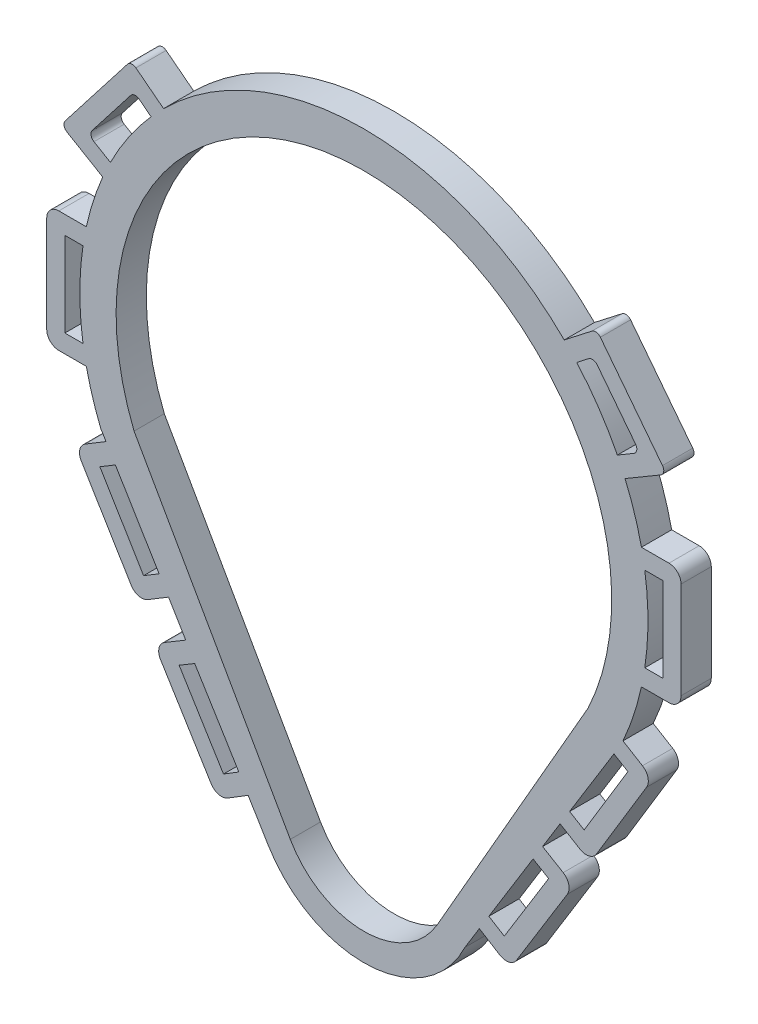
SolidWorks part; units mm, degrees
ref_plane "Front Plane" through (0, 0, 0) normal (0, 0, 1) x (1, 0, 0)
ref_plane "Top Plane" through (0, 0, 0) normal (0, 1, 0) x (1, 0, 0)
ref_plane "Right Plane" through (0, 0, 0) normal (1, 0, 0) x (0, 0, -1)
sketch "Sketch1" plane through (0, 0, 0) normal (0, 0, 1) x (1, 0, 0)
  line L0 (0, 41) -> (0, -67) construction
  line L5 (0, 0) -> (0, -54) construction
  line L6 (37.1057, -17.4403) -> (11.3127, -72.3172) construction
  line L7 (42.5358, -19.9925) -> (16.7428, -74.8694) construction
  line L8 (-38.0251, -15.3328) -> (-11.3182, -72.3056) construction
  line L9 (-43.5255, -17.735) -> (-16.7509, -74.8522) construction
  line L10 (-38.0251, -15.3328) -> (-12.1778, -60.9066)
  line L11 (-43.5255, -17.735) -> (-15.8341, -63.5669)
  line L12 (37.1057, -17.4403) -> (12.1446, -60.9649)
  line L13 (42.5358, -19.9925) -> (16.7077, -61.9433)
  arc A0 (37.1057, -17.4403) -> (-38.0251, -15.3328) centre (0, 0) ccw
  arc A2 (42.5358, -19.9925) -> (-43.5255, -17.735) centre (0, 0) ccw
  arc A4 (-12.1778, -60.9066) -> (12.1446, -60.9649) centre (0, -54) ccw
  arc A5 (-16.7509, -74.8522) -> (16.7428, -74.8694) centre (0, -67) ccw construction
  arc A6 (-11.3182, -72.3056) -> (11.3127, -72.3172) centre (0, -67) ccw construction
  arc A7 (-15.8341, -63.5669) -> (16.7077, -61.9433) centre (0, -54) ccw
  dimension "D1" = 6
  dimension "D2" = 41
  dimension "D3" = 14
  dimension "D6" = 18.4999
  dimension "D4" = 67
  dimension "D5" = 54
extrude "Boss-Extrude1" add sketch "Sketch1" along normal blind 5
sketch "Sketch3" plane through (0, 0, 5) normal (0, 0, 1) x (1, 0, 0)
  line L0 (-35.214, 31.1284) -> (-37.1889, 32.6612)
  line L1 (-41.9377, 21.2186) -> (-44.6629, 22.8236)
  line L2 (-38.592, 32.4844) -> (-44.9454, 24.2984)
  line L3 (-35.214, 31.1284) -> (-41.9377, 21.2186)
  line L4 (-31.1514, 31.7728) -> (-37.7195, 36.8706)
  line L5 (-39.1226, 36.6937) -> (-49.4061, 23.444)
  line L6 (-41.0353, 17.2054) -> (-49.1237, 21.9692)
  line L7 (-31.1514, 31.7728) -> (-41.0353, 17.2054)
  line L8 (0, 0) -> (0, 76.5871) construction
  line L17 (-35.214, 31.1284) -> (-37.9789, 33.2743) construction
  line L18 (-37.9789, 33.2743) -> (-45.6424, 23.4005) construction
  line L19 (-31.1514, 31.7728) -> (-38.5094, 37.4837) construction
  line L20 (-38.5094, 37.4837) -> (-50.1031, 22.5461) construction
  line L21 (-41.0353, 17.2054) -> (-50.1031, 22.5461) construction
  line L22 (-41.9377, 21.2186) -> (-45.6424, 23.4005) construction
  line L23 (31.1514, 31.7728) -> (41.0353, 17.2054)
  line L24 (41.0353, 17.2054) -> (49.1237, 21.9692)
  line L25 (39.1226, 36.6937) -> (49.4061, 23.444)
  line L26 (31.1514, 31.7728) -> (37.7195, 36.8706)
  line L27 (35.214, 31.1284) -> (41.9377, 21.2186)
  line L28 (38.592, 32.4844) -> (44.9454, 24.2984)
  line L29 (41.9377, 21.2186) -> (44.6629, 22.8236)
  line L30 (35.214, 31.1284) -> (37.1889, 32.6612)
  circle A0 centre (38.8928, 26.3885) radius 6 construction
  circle A1 centre (-38.8928, 26.3885) radius 6 construction
  arc A2 (42.5358, -19.9925) -> (-43.5255, -17.735) centre (0, 0) ccw construction
  arc A3 (44.6629, 22.8236) -> (44.9454, 24.2984) centre (44.1554, 23.6853) ccw
  arc A4 (-37.1889, 32.6612) -> (-38.592, 32.4844) centre (-37.8021, 31.8712) ccw
  arc A5 (-37.7195, 36.8706) -> (-39.1226, 36.6937) centre (-38.3326, 36.0806) ccw
  arc A6 (-49.1237, 21.9692) -> (-49.4061, 23.444) centre (-48.6162, 22.8309) cw
  arc A7 (-44.6629, 22.8236) -> (-44.9454, 24.2984) centre (-44.1554, 23.6853) cw
  arc A12 (49.1237, 21.9692) -> (49.4061, 23.444) centre (48.6162, 22.8309) ccw
  arc A13 (37.7195, 36.8706) -> (39.1226, 36.6937) centre (38.3326, 36.0806) cw
  arc A14 (37.1889, 32.6612) -> (38.592, 32.4844) centre (37.8021, 31.8712) cw
  point P29 (-39.9539, 34.8072)
  point P33 (-38.5094, 37.4837)
  point P48 (38.5094, 37.4837)
  point P49 (39.9539, 34.8072)
  dimension "D1" = 3
  dimension "D2" = 12
  dimension "D3" = 2.5
extrude "1" add sketch "Sketch3" against normal blind 5
sketch "Sketch4" plane through (0, 0, 5) normal (0, 0, 1) x (1, 0, 0)
  line L2 (0, 0) -> (0, 26.9586) construction
  line L5 (-46.4758, 7) -> (-46.4758, -7)
  line L6 (-46.4758, 7) -> (-49.4758, 7)
  line L7 (-49.4758, 7) -> (-49.4758, -7)
  line L8 (-49.4758, -7) -> (-46.4758, -7)
  line L9 (-43.4758, 10) -> (-50.4758, 10)
  line L10 (-52.4758, 8) -> (-52.4758, -8)
  line L11 (-50.4758, -10) -> (-43.4758, -10)
  line L12 (-43.4758, 10) -> (-43.4758, -10)
  line L13 (43.4758, 10) -> (43.4758, -10)
  line L14 (50.4758, -10) -> (43.4758, -10)
  line L15 (52.4758, 8) -> (52.4758, -8)
  line L16 (43.4758, 10) -> (50.4758, 10)
  line L17 (49.4758, -7) -> (46.4758, -7)
  line L18 (49.4758, 7) -> (49.4758, -7)
  line L19 (46.4758, 7) -> (49.4758, 7)
  line L20 (46.4758, 7) -> (46.4758, -7)
  line L21 (-52.4758, -10) -> (-43.4758, -10) construction
  line L22 (-52.4758, 10) -> (-52.4758, -10) construction
  line L23 (-43.4758, 10) -> (-52.4758, 10) construction
  arc A0 (50.4758, -10) -> (52.4758, -8) centre (50.4758, -8) ccw
  arc A5 (-43.2114, 18.4871) -> (-43.5255, -17.735) centre (0, 0) ccw construction
  arc A6 (52.4758, 8) -> (50.4758, 10) centre (50.4758, 8) ccw
  arc A7 (-50.4758, -10) -> (-52.4758, -8) centre (-50.4758, -8) cw
  arc A8 (-52.4758, 8) -> (-50.4758, 10) centre (-50.4758, 8) cw
  point P24 (52.4758, -10)
  point P27 (52.4758, 10)
  point P31 (-52.4758, -10)
  dimension "D1" = 2
  dimension "D2" = 14
  dimension "D3" = 3
  dimension "D4" = 3
extrude "2" add sketch "Sketch4" against normal blind 5
sketch "Sketch5" plane through (0, 0, 5) normal (0, 0, 1) x (1, 0, 0)
  line L0 (-41.1186, -21.7187) -> (-43.6863, -23.2701)
  line L1 (-43.5255, -17.735) -> (-15.8341, -63.5669) construction
  line L2 (-43.6863, -23.2701) -> (-36.4464, -35.2528)
  line L3 (-36.4464, -35.2528) -> (-33.8787, -33.7014)
  line L4 (-41.1186, -21.7187) -> (-33.8787, -33.7014)
  line L5 (-40.1022, -17.5996) -> (-46.0936, -21.2196)
  line L6 (-46.7711, -23.9656) -> (-38.497, -37.6601)
  line L7 (-35.7509, -38.3377) -> (-29.7596, -34.7177)
  line L8 (-40.1022, -17.5996) -> (-29.7596, -34.7177)
  line L9 (0, 0) -> (0, -46.5074) construction
  line L10 (40.1022, -17.5996) -> (29.7596, -34.7177)
  line L11 (35.7509, -38.3377) -> (29.7596, -34.7177)
  line L12 (46.7711, -23.9656) -> (38.497, -37.6601)
  line L13 (40.1022, -17.5996) -> (46.0936, -21.2196)
  line L14 (41.1186, -21.7187) -> (33.8787, -33.7014)
  line L15 (36.4464, -35.2528) -> (33.8787, -33.7014)
  line L16 (43.6863, -23.2701) -> (36.4464, -35.2528)
  line L17 (41.1186, -21.7187) -> (43.6863, -23.2701)
  line L18 (-37.4627, -39.3719) -> (-29.7596, -34.7177) construction
  line L19 (-47.8054, -22.2538) -> (-37.4627, -39.3719) construction
  line L20 (-40.1022, -17.5996) -> (-47.8054, -22.2538) construction
  arc A0 (-35.7509, -38.3377) -> (-38.497, -37.6601) centre (-36.7852, -36.6259) cw
  arc A1 (-46.7711, -23.9656) -> (-46.0936, -21.2196) centre (-45.0593, -22.9314) cw
  arc A2 (35.7509, -38.3377) -> (38.497, -37.6601) centre (36.7852, -36.6259) ccw
  arc A3 (46.0936, -21.2196) -> (46.7711, -23.9656) centre (45.0593, -22.9314) cw
  point P24 (-37.4627, -39.3719)
  point P30 (37.4627, -39.3719)
  dimension "D4" = 2
  dimension "D1" = 3
  dimension "D2" = 14
  dimension "D3" = 3
extrude "3" add sketch "Sketch5" against normal blind 5
sketch "Sketch2" plane through (0, 0, 5) normal (0, 0, 1) x (1, 0, 0)
  line L1 (34.7204, -44.1302) -> (26.9879, -39.5238) construction
  line L4 (0, 49.5385) -> (0, -93.5909) construction
  line L18 (27.9925, -43.6143) -> (20.6756, -55.4986)
  line L19 (16.7077, -61.9433) -> (32.4639, -36.3517) construction
  line L20 (20.6756, -55.4986) -> (23.2302, -57.0715)
  line L21 (23.2302, -57.0715) -> (30.5698, -45.1496)
  line L22 (30.5698, -45.1496) -> (27.9925, -43.6143)
  line L23 (25.2606, -59.4958) -> (33.6565, -45.8584)
  line L24 (32.9769, -43.0916) -> (26.9879, -39.5238)
  line L25 (26.9879, -39.5238) -> (16.5481, -56.4805)
  line L26 (16.5481, -56.4805) -> (22.509, -60.1504)
  line L27 (-16.5481, -56.4805) -> (-22.5088, -60.1503)
  line L28 (-26.9879, -39.5238) -> (-16.5481, -56.4805)
  line L29 (-32.9769, -43.0916) -> (-26.9879, -39.5238)
  line L30 (-25.2605, -59.4958) -> (-33.6565, -45.8584)
  line L31 (-30.5698, -45.1496) -> (-27.9925, -43.6143)
  line L32 (-23.2302, -57.0715) -> (-30.5698, -45.1496)
  line L33 (-20.6756, -55.4986) -> (-23.2302, -57.0715)
  line L34 (-27.9925, -43.6143) -> (-20.6756, -55.4986)
  line L35 (24.2121, -61.199) -> (34.7204, -44.1302) construction
  line L36 (16.5481, -56.4805) -> (24.2121, -61.199) construction
  arc A0 (32.9769, -43.0916) -> (33.6565, -45.8584) centre (31.9534, -44.8098) cw
  arc A1 (25.2606, -59.4958) -> (22.509, -60.1504) centre (23.5575, -58.4473) cw
  arc A2 (-22.5088, -60.1503) -> (-25.2605, -59.4958) centre (-23.5574, -58.4472) cw
  arc A3 (-33.6565, -45.8584) -> (-32.9769, -43.0916) centre (-31.9533, -44.8098) cw
  point P20 (34.7204, -44.1302)
  point P32 (-34.7204, -44.1302)
  dimension "D3" = 2
  dimension "D1" = 3
  dimension "D2" = 3
  dimension "D4" = 14
  dimension "D5" = 3
extrude "4" add sketch "Sketch2" against normal blind 5
